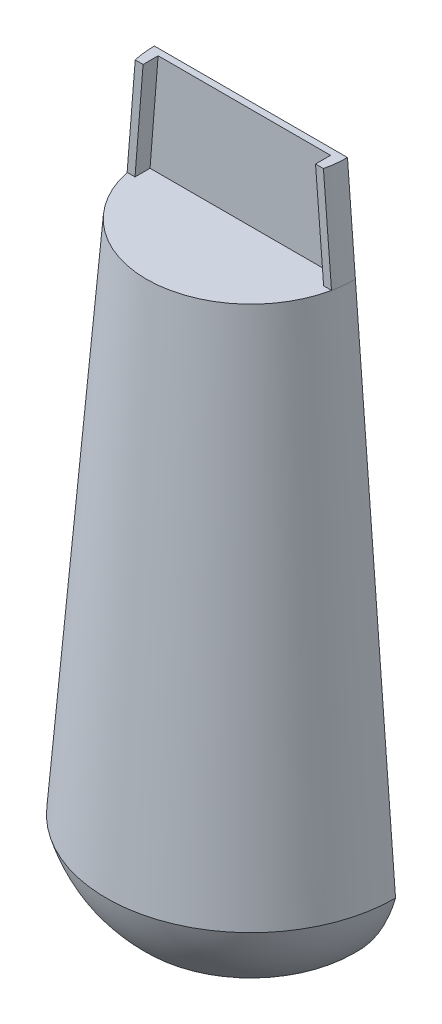
SolidWorks part; units mm, degrees
ref_plane "Front Plane" through (0, 0, 0) normal (0, 0, 1) x (1, 0, 0)
ref_plane "Top Plane" through (0, 0, 0) normal (0, 1, 0) x (1, 0, 0)
ref_plane "Right Plane" through (0, 0, 0) normal (1, 0, 0) x (0, 0, -1)
sketch "Sketch1" plane through (0, 0, 0) normal (0, 0, 1) x (1, 0, 0)
  line L0 (27.686, 0) -> (22.606, 0)
  line L1 (22.606, 0) -> (22.606, 1.8288)
  line L2 (28.829, 4.191) -> (22.606, 4.191)
  line L3 (22.606, 4.191) -> (22.606, 5.8928)
  line L4 (22.606, 5.8928) -> (30.607, 5.8928)
  line L5 (36.5429, 18.669) -> (0, 18.669)
  line L6 (0, 18.669) -> (0, 185.547)
  line L7 (0, 185.547) -> (26.0985, 185.547)
  line L8 (26.0985, 185.547) -> (39.0906, 18.669)
  line L9 (36.5429, 18.669) -> (35.5415, 31.5318) construction
  line L10 (27.686, 0) -> (-4.9317, -30.4165) construction
  line L11 (39.0906, 18.669) -> (57.9001, 81.973) construction
  line L12 (34.3825, 10.171) -> (26.8315, 1.6146) construction
  line L13 (30.8955, 5.835) -> (26.7625, 2.547) construction
  line L14 (22.606, 1.8288) -> (0, 1.8288) construction
  spline S0 degree 3 poles (27.686, 0) (33.0192, 4.9733) (36.7329, 10.7342) (39.0906, 18.669) knots 0 0 0 0 1 1 1 1
  spline S1 degree 3 poles (22.606, 1.8288) (25.0412, 1.8288) (27.1069, 2.821) (28.829, 4.191) knots 0 0 0 0 0.286843 0.286843 0.286843 0.286843
  spline S2 degree 2 poles (30.607, 5.8928) (35.3264, 11.2406) (36.5429, 18.669) knots 0.392904 0.392904 0.392904 1 1 1
  dimension "D1" = 185.547
  dimension "D2" = 39.0906
  dimension "D3" = 18.669
  dimension "D4" = 22.606
  dimension "D5" = 5.08
  dimension "D6" = 1.8288
  dimension "D7" = 2.3622
  dimension "D8" = 6.223
  dimension "D9" = 1.7018
  dimension "D10" = 8.001
  dimension "D11" = 26.0985
  dimension "D12" = 2.54
  dimension "D13" = 43
  dimension "D14" = 21
revolve "Revolve1" add sketch "Sketch1" angle 180 about L6 reverse direction yes
sketch "Sketch2" plane through (0, 185.547, 0) normal (0, 1, 0) x (1, 0, 0)
  line L0 (-23.3045, -1.778) -> (23.3045, -1.778)
  line L1 (23.3045, -1.778) -> (23.3045, -5.842)
  line L2 (23.3045, -5.842) -> (25.4362, -5.842)
  line L3 (25.4362, -5.842) -> (28.0363, -5.842)
  line L4 (-23.3045, -1.778) -> (-23.3045, -5.842)
  line L5 (-23.3045, -5.842) -> (-25.4362, -5.842)
  line L6 (-25.4362, -5.842) -> (-28.0363, -5.842)
  arc A1 (-26.0985, 0) -> (26.0985, 0) centre (0, 0) ccw construction
  arc A2 (-28.6385, 0) -> (28.6385, 0) centre (0, 0) ccw
  arc A3 (-28.0363, -5.842) -> (28.0363, -5.842) centre (0, 0) ccw
  point P6 (0, -1.778)
  dimension "D1" = 2.54
  dimension "D2" = 46.609
  dimension "D3" = 4.064
  dimension "D4" = 5.842
  dimension "D5" = 2.1317
sketch "Sketch3" plane through (0, 0, 0) normal (0, 0, 1) x (1, 0, 0)
  line L0 (-39.0906, 158.115) -> (39.0906, 158.115)
  dimension "D1" = 158.115
split line "Split Line1"
ref_plane "Plane1" through (0, 158.115, 0) normal (0, 1, 0) x (1, 0, 0)
sketch "Sketch4" plane through (0, 158.115, 0) normal (0, 1, 0) x (1, 0, 0)
  line L0 (-25.4914, -1.778) -> (25.4914, -1.778)
  line L1 (25.4914, -1.778) -> (25.4914, -5.842)
  line L2 (25.4914, -5.842) -> (27.6232, -5.842)
  line L3 (27.6232, -5.842) -> (30.2146, -5.842)
  line L4 (-25.4914, -1.778) -> (-25.4914, -5.842)
  line L5 (-25.4914, -5.842) -> (-27.6232, -5.842)
  line L6 (-27.6232, -5.842) -> (-30.2146, -5.842)
  arc A1 (-28.2342, 0) -> (28.2342, 0) centre (0, 0) ccw construction
  arc A2 (-30.7742, 0) -> (30.7742, 0) centre (0, 0) ccw
  arc A3 (-30.2146, -5.842) -> (30.2146, -5.842) centre (0, 0) ccw
  point P6 (0, -1.778)
  dimension "D2" = 4.064
  dimension "D3" = 5.842
  dimension "D4" = 2.1317
  dimension "D1" = 2.54
loft "Cut-Loft1" cut profiles "Sketch2", "Sketch4" connector at (28.0363, 185.547, 5.842) connector at (30.2146, 158.115, 5.842)
sketch "Sketch5" plane through (0, 0, 0) normal (1, 0, 0) x (0, 0, -1)
  line L0 (-27.686, 30.0736) -> (-27.686, 115.9256)
  line L1 (-28.2342, 158.115) -> (-39.0906, 18.669) construction
  line L2 (-31.242, 119.4816) -> (-39.0906, 18.669)
  arc A0 (-39.0906, 18.669) -> (-27.686, 30.0736) centre (-39.0906, 30.0736) ccw
  arc A1 (-27.686, 115.9256) -> (-31.242, 119.4816) centre (-31.242, 115.9256) ccw
  dimension "D1" = 27.686
  dimension "D2" = 85.852
equation "\"D2@Sketch4\"= \"D3@Sketch2\""
equation "\"D3@Sketch4\"= \"D4@Sketch2\""
equation "\"D4@Sketch4\"= \"D5@Sketch2\""
